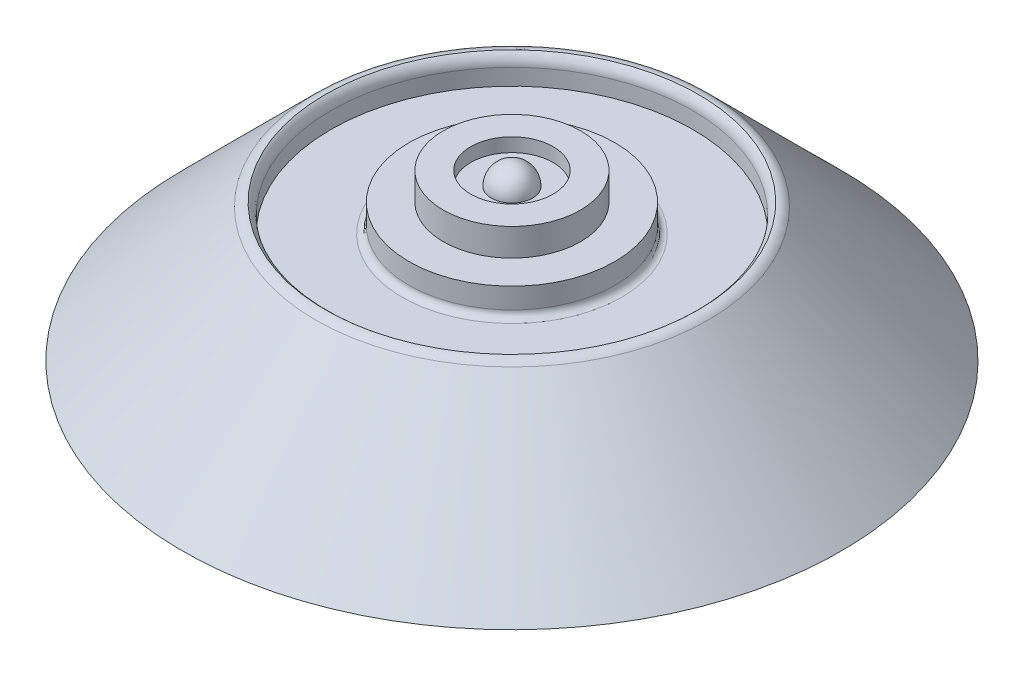
SolidWorks part; units mm, degrees
ref_plane "Front Plane" through (0, 0, 0) normal (0, 0, 1) x (1, 0, 0)
ref_plane "Top Plane" through (0, 0, 0) normal (0, 1, 0) x (1, 0, 0)
ref_plane "Right Plane" through (0, 0, 0) normal (1, 0, 0) x (0, 0, -1)
sketch "Sketch1" plane through (0, 0, 0) normal (0, 0, 1) x (1, 0, 0)
  line L0 (0, 0) -> (0, -25.4)
  line L1 (0, -25.4) -> (60.96, -25.4)
  line L2 (60.96, -25.4) -> (35.56, 0)
  line L3 (35.56, 0) -> (0, 0)
  dimension "D1" = 35.56
  dimension "D2" = 60.96
  dimension "D3" = 0
  dimension "D4" = 25.4
revolve "Revolve1" add sketch "Sketch1" angle 360 about L0
fillet "Fillet1" radius 2.54 1 edges at (-35.56, 0, 0)
sketch "Sketch3" plane through (0, 0, 0) normal (0, 1, 0) x (1, 0, 0)
  circle A0 centre (0, 0) radius 33.4558
  circle A1 centre (0, 0) radius 19.05
  dimension "D1" = 66.9116
  dimension "D2" = 38.1
extrude "Cut-Extrude1" cut sketch "Sketch3" against normal blind 5.08
fillet "Fillet4" radius 2.54 1 edges at (-33.4558, 0, 0)
sketch "Sketch4" plane through (0, 0, 0) normal (0, 1, 0) x (1, 0, 0)
  circle A0 centre (0, 0) radius 12.7
  dimension "D1" = 25.4
extrude "Boss-Extrude1" add sketch "Sketch4" along normal blind 5.08 contours A0
sketch "Sketch5" plane through (0, 5.08, 0) normal (0, 1, 0) x (1, 0, 0)
  circle A0 centre (0, 0) radius 7.62
  dimension "D1" = 15.24
extrude "Cut-Extrude2" cut sketch "Sketch5" against normal blind 2.54
fillet "Fillet6" radius 1.27 1 edges at (-19.05, -5.08, 0)
sketch "Sketch6" plane through (0, 2.54, 0) normal (0, 1, 0) x (1, 0, 0)
  line L0 (0, -3.81) -> (0, 3.81)
  arc A0 (0, 3.81) -> (0, -3.81) centre (0, 0) ccw
  dimension "D1" = 7.62
  dimension "D2" = 0
revolve "Revolve2" add sketch "Sketch6" angle 180 about L0
scale "Scale1" scale about centroid uniform scaling yes scale factor 0.5
